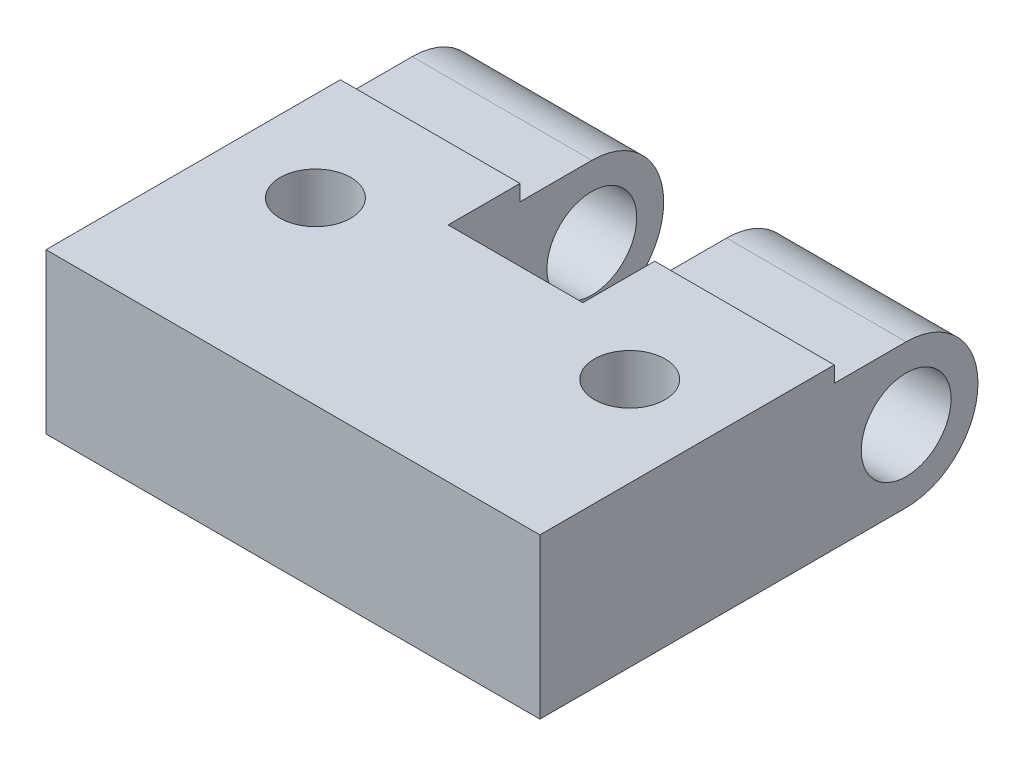
SolidWorks part; units mm, degrees
ref_plane "Front" through (0, 0, 0) normal (0, 0, 1) x (1, 0, 0)
ref_plane "Top" through (0, 0, 0) normal (0, 1, 0) x (1, 0, 0)
ref_plane "Right" through (0, 0, 0) normal (1, 0, 0) x (0, 0, -1)
sketch "Sketch2" plane through (0, 0, 0) normal (1, 0, 0) x (0, 0, -1)
  line L0 (0, 5.08) -> (0, 0)
  line L1 (0, 0) -> (13.1956, 0)
  line L2 (0, 0) -> (0, 5.08)
  line L3 (0, 5.08) -> (13.1956, 5.08)
  line L4 (13.1956, 0) -> (13.1956, 5.08)
  line L5 (0, 5.08) -> (-6.35, 5.08)
  line L6 (0, 0) -> (-6.35, 0)
  line L7 (-6.35, 5.08) -> (-6.35, 0)
  circle A0 centre (6.5978, 2.54) radius 1.5875
  arc A1 (6.5978, 5.08) -> (6.5978, 0) centre (6.5978, 2.54) cw
  point P7 (6.5978, 5.08)
  point P8 (6.5978, 0)
  dimension "D1" = 5.08
  dimension "D2" = 6.35
extrude "Boss-Extrude1" add sketch "Sketch2" along normal blind 6.35 contours L5 L7 L6 L0 | A1 L3 L0 L1 A0 region at (0, 2.54, -3.8093) region at (0, 2.54, 3.175)
sketch "Sketch3" plane through (0, 5.08, 0) normal (0, 1, 0) x (1, 0, 0)
  line L0 (3.175, -6.35) -> (3.175, 0)
  line L1 (6.35, -6.35) -> (0, -6.35) construction
  circle A0 centre (3.175, 0) radius 1.25
  dimension "D1" = 6.35
extrude "Cut-Extrude1" cut sketch "Sketch3" against normal blind 10 contours A0 region at (4.0339, 5.08, 0.8589)
sketch "Sketch4" plane through (6.35, 0, 0) normal (1, 0, 0) x (0, 0, -1)
  line L0 (6.5978, 2.54) -> (2.6291, 2.54)
  line L1 (6.5978, 2.54) -> (1.5178, 2.54)
  line L2 (6.5978, 0) -> (-6.35, 0) construction
  line L3 (1.5178, 0) -> (-6.35, 0)
  line L4 (1.5178, 0) -> (1.5178, 5.08)
  line L5 (1.5178, 5.08) -> (-6.35, 5.08)
  line L6 (-6.35, 0) -> (-6.35, 5.08)
  line M2 (6.5978, 5.08) -> (-6.35, 5.08)
  line M3 (-6.35, 5.08) -> (-6.35, 0)
  line M4 (-6.35, 0) -> (6.5978, 0)
  dimension "D1" = 3.9688
  dimension "D2" = 5.08
extrude "Boss-Extrude2" add sketch "Sketch4" along normal blind 4.7625 contours L4 M4 M2 M3 region at (6.35, 2.54, 2.4161)
ref_plane "Plane1" through (8.7313, 0, 0) normal (1, 0, 0) x (0, 0, -1)
mirror "Mirror1" about plane through (8.7313, 0, 0) normal (1, 0, 0) of "Cut-Extrude1", "Boss-Extrude1"
sketch "Sketch6" plane through (0, 5.08, 0) normal (0, 1, 0) x (1, 0, 0)
  line L0 (6.35, 4.0578) -> (0, 4.0578)
  line L1 (6.35, 6.5978) -> (6.35, 1.5178) construction
  line L2 (0, 6.5978) -> (0, -6.35) construction
  line L3 (0, 4.0578) -> (0, -6.35)
  line L4 (0, -6.35) -> (17.4625, -6.35)
  line L5 (17.4625, -6.35) -> (17.4625, 4.0578)
  line L6 (17.4625, 6.5978) -> (17.4625, -6.35) construction
  line L7 (17.4625, 4.0578) -> (11.1125, 4.0578)
  line L8 (11.1125, 6.5978) -> (11.1125, 1.5178) construction
  line L9 (11.1125, 4.0578) -> (11.1125, 1.5178)
  line L10 (11.1125, 1.5178) -> (6.35, 1.5178)
  line L11 (6.35, 1.5178) -> (6.35, 4.0578)
extrude "Boss-Extrude3" add sketch "Sketch6" along normal blind 0.5625
sketch "Sketch7" plane through (0, 5.08, 0) normal (0, -1, 0) x (1, 0, 0)
  circle A0 centre (14.2875, 0) radius 1.25
  circle A1 centre (3.175, 0) radius 1.25
extrude "Cut-Extrude2" cut sketch "Sketch7" against normal through all both and the other way through all
